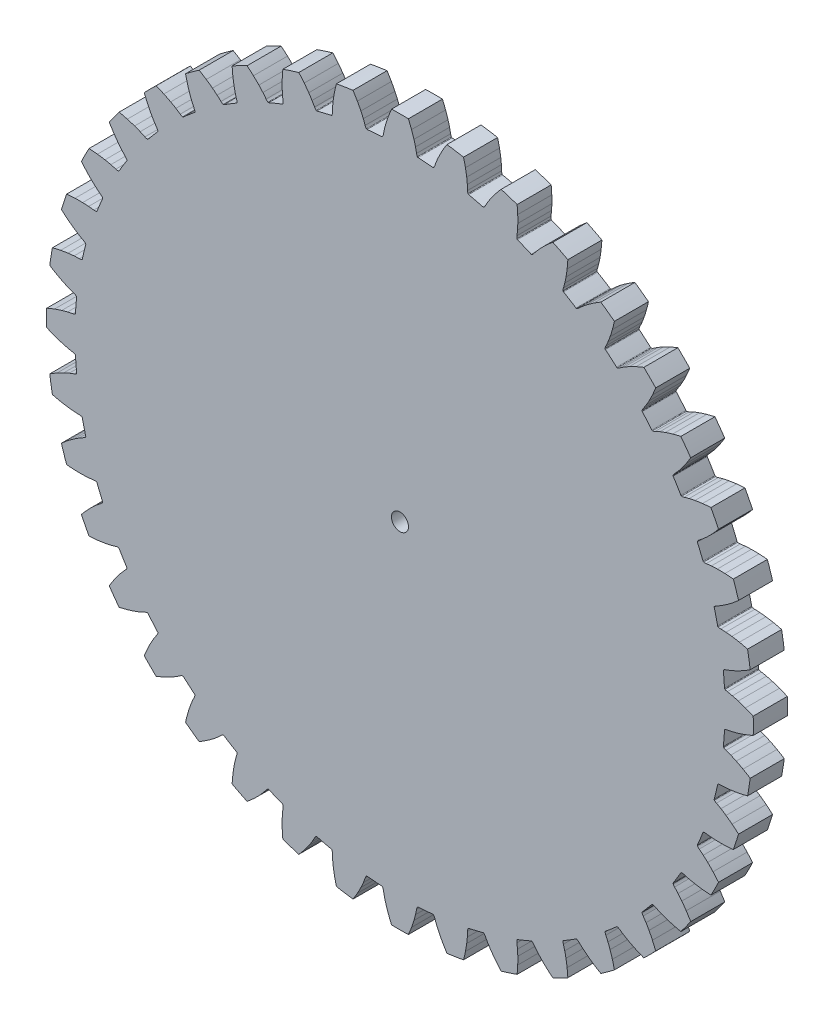
SolidWorks part; units mm, degrees
ref_plane "Front Plane" through (0, 0, 0) normal (0, 0, 1) x (1, 0, 0)
ref_plane "Top Plane" through (0, 0, 0) normal (0, 1, 0) x (1, 0, 0)
ref_plane "Right Plane" through (0, 0, 0) normal (1, 0, 0) x (0, 0, -1)
sketch "Model" plane through (0, 0, 0) normal (0, 0, 1) x (1, 0, 0)
  arc A1 (60.4326, -4.7561) -> (60.5251, -3.3796) centre (0, 0) ccw
  arc A2 (60.6099, -3.2458) -> (60.5251, -3.3796) centre (60.6875, -3.3887) ccw
  arc A3 (61.0557, -3.0916) -> (60.6099, -3.2458) centre (61.2975, -4.5122) ccw
  arc A4 (61.0557, -3.0916) -> (62.0044, -2.8977) centre (58.5908, 11.3846) ccw
  arc A5 (62.0044, -2.8977) -> (63.0847, -2.6067) centre (57.4472, 16.1693) ccw
  arc A6 (63.0847, -2.6067) -> (64.4306, -2.1546) centre (56.7644, 18.4435) ccw
  arc A7 (64.4306, -2.1546) -> (65.8858, -1.5642) centre (55.0531, 23.0418) ccw
  arc A8 (65.8858, -1.5642) -> (65.8858, 1.5642) centre (0, 0) ccw
  arc A9 (65.8858, 1.5642) -> (64.4306, 2.1546) centre (55.0531, -23.0418) ccw
  arc A10 (64.4306, 2.1546) -> (63.0847, 2.6067) centre (56.7644, -18.4435) ccw
  arc A11 (63.0847, 2.6067) -> (62.0044, 2.8977) centre (57.4472, -16.1693) ccw
  arc A12 (62.0044, 2.8977) -> (61.0557, 3.0916) centre (58.5908, -11.3846) ccw
  arc A13 (60.6099, 3.2458) -> (61.0557, 3.0916) centre (61.2975, 4.5122) ccw
  arc A14 (60.5251, 3.3796) -> (60.6099, 3.2458) centre (60.6875, 3.3887) ccw
  arc A15 (60.5251, 3.3796) -> (60.3087, 6.1302) centre (0, 0) ccw
  arc A16 (60.3715, 6.2757) -> (60.3087, 6.1302) centre (60.4705, 6.1466) ccw
  arc A17 (60.7876, 6.4977) -> (60.3715, 6.2757) centre (61.2487, 5.1324) ccw
  arc A18 (60.7876, 6.4977) -> (61.6943, 6.8376) centre (56.0885, 20.41) ccw
  arc A19 (61.6943, 6.8376) -> (62.7158, 7.294) centre (54.2105, 24.957) ccw
  arc A20 (62.7158, 7.294) -> (63.9745, 7.9511) centre (53.1804, 27.0964) ccw
  arc A21 (63.9745, 7.9511) -> (65.3193, 8.7619) centre (50.7708, 31.3703) ccw
  arc A22 (65.3193, 8.7619) -> (64.8299, 11.8517) centre (0, 0) ccw
  arc A23 (64.8299, 11.8517) -> (63.3003, 12.2073) centre (57.9798, -14.1459) ccw
  arc A24 (63.3003, 12.2073) -> (61.9002, 12.4432) centre (58.9508, -9.3365) ccw
  arc A25 (61.9002, 12.4432) -> (60.7877, 12.5616) centre (59.2694, -6.9835) ccw
  arc A26 (60.7877, 12.5616) -> (59.8203, 12.6047) centre (59.6504, -2.0788) ccw
  arc A27 (59.356, 12.6873) -> (59.8203, 12.6047) centre (59.837, 14.0457) ccw
  arc A28 (59.2513, 12.8063) -> (59.356, 12.6873) centre (59.4102, 12.8406) ccw
  arc A29 (59.2513, 12.8063) -> (58.6072, 15.4891) centre (0, 0) ccw
  arc A30 (58.6465, 15.6426) -> (58.6072, 15.4891) centre (58.7644, 15.5306) ccw
  arc A31 (59.0227, 15.9269) -> (58.6465, 15.6426) centre (59.6918, 14.6506) ccw
  arc A32 (59.0227, 15.9269) -> (59.8651, 16.4045) centre (52.2052, 28.9329) ccw
  arc A33 (59.8651, 16.4045) -> (60.8026, 17.0152) centre (49.639, 33.1301) ccw
  arc A34 (60.8026, 17.0152) -> (61.943, 17.861) centre (48.2868, 35.082) ccw
  arc A35 (61.943, 17.861) -> (63.1444, 18.8722) centre (45.2383, 38.9263) ccw
  arc A36 (63.1444, 18.8722) -> (62.1777, 21.8474) centre (0, 0) ccw
  arc A37 (62.1777, 21.8474) -> (60.6114, 21.9594) centre (59.4789, -4.9017) ccw
  arc A38 (60.6114, 21.9594) -> (59.1916, 21.9733) centre (59.6855, 0.0004) ccw
  arc A39 (59.1916, 21.9733) -> (58.0742, 21.9163) centre (59.6322, 2.3742) ccw
  arc A40 (58.0742, 21.9163) -> (57.112, 21.8075) centre (59.2412, 7.2782) ccw
  arc A41 (56.6405, 21.8164) -> (57.112, 21.8075) centre (56.9031, 23.2334) ccw
  arc A42 (56.5185, 21.9175) -> (56.6405, 21.8164) centre (56.6701, 21.9763) ccw
  arc A43 (56.5185, 21.9175) -> (55.4626, 24.4666) centre (0, 0) ccw
  arc A44 (55.4774, 24.6243) -> (55.4626, 24.4666) centre (55.6114, 24.5322) ccw
  arc A45 (55.8045, 24.9641) -> (55.4774, 24.6243) centre (56.665, 23.8081) ccw
  arc A46 (55.8045, 24.9641) -> (56.5618, 25.5675) centre (47.0363, 36.7434) ccw
  arc A47 (56.5618, 25.5675) -> (57.3922, 26.3173) centre (43.8451, 40.4875) ccw
  arc A48 (57.3922, 26.3173) -> (58.3863, 27.3311) centre (42.2043, 42.2038) ccw
  arc A49 (58.3863, 27.3311) -> (59.4147, 28.5178) centre (38.5919, 45.5239) ccw
  arc A50 (59.4147, 28.5178) -> (57.9945, 31.3052) centre (0, 0) ccw
  arc A51 (57.9945, 31.3052) -> (56.4299, 31.1707) centre (59.5134, 4.4632) ccw
  arc A52 (56.4299, 31.1707) -> (55.0254, 30.9624) centre (58.9507, 9.3372) ccw
  arc A53 (55.0254, 30.9624) -> (53.9308, 30.7312) centre (58.5266, 11.6735) ccw
  arc A54 (53.9308, 30.7312) -> (52.9974, 30.4733) centre (57.3733, 16.456) ccw
  arc A55 (52.5303, 30.4083) -> (52.9974, 30.4733) centre (52.568, 31.8489) ccw
  arc A56 (52.394, 30.4891) -> (52.5303, 30.4083) centre (52.5345, 30.5709) ccw
  arc A57 (52.394, 30.4891) -> (50.9524, 32.8416) centre (0, 0) ccw
  arc A58 (50.9423, 32.9997) -> (50.9524, 32.8416) centre (51.0891, 32.9297) ccw
  arc A59 (51.2123, 33.3865) -> (50.9423, 32.9997) centre (52.243, 32.3793) ccw
  arc A60 (51.2123, 33.3865) -> (51.8658, 34.101) centre (40.7093, 43.6491) ccw
  arc A61 (51.8658, 34.101) -> (52.5687, 34.9714) centre (36.9717, 46.8479) ccw
  arc A62 (52.5687, 34.9714) -> (53.392, 36.1282) centre (35.0826, 48.2864) ccw
  arc A63 (53.392, 36.1282) -> (54.2221, 37.4613) centre (30.9953, 51.0006) ccw
  arc A64 (54.2221, 37.4613) -> (52.3833, 39.9921) centre (0, 0) ccw
  arc A65 (52.3833, 39.9921) -> (50.859, 39.6145) centre (58.0825, 13.7182) ccw
  arc A66 (50.859, 39.6145) -> (49.5044, 39.1891) centre (56.7642, 18.4442) ccw
  arc A67 (49.5044, 39.1891) -> (48.4594, 38.7895) centre (55.9799, 20.6854) ccw
  arc A68 (48.4594, 38.7895) -> (47.5779, 38.3888) centre (54.0927, 25.2285) ccw
  arc A69 (47.1266, 38.2515) -> (47.5779, 38.3888) centre (46.9385, 39.6803) ccw
  arc A70 (46.9794, 38.31) -> (47.1266, 38.2515) centre (47.1054, 38.4128) ccw
  arc A71 (46.9794, 38.31) -> (45.1875, 40.408) centre (0, 0) ccw
  arc A72 (45.1528, 40.5626) -> (45.1875, 40.408) centre (45.3087, 40.5164) ccw
  arc A73 (45.359, 40.9868) -> (45.1528, 40.5626) centre (46.5345, 40.1533) ccw
  arc A74 (45.359, 40.9868) -> (45.8927, 41.7947) centre (33.3799, 49.4801) ccw
  arc A75 (45.8927, 41.7947) -> (46.4508, 42.7644) centre (29.1879, 52.0548) ccw
  arc A76 (46.4508, 42.7644) -> (47.0829, 44.0358) centre (27.097, 53.1801) ccw
  arc A77 (47.0829, 44.0358) -> (47.6943, 45.4822) centre (22.6354, 55.2214) ccw
  arc A78 (47.6943, 45.4822) -> (45.4822, 47.6943) centre (0, 0) ccw
  arc A79 (45.4822, 47.6943) -> (44.0358, 47.0829) centre (55.2214, 22.6354) ccw
  arc A80 (44.0358, 47.0829) -> (42.7644, 46.4508) centre (53.1801, 27.097) ccw
  arc A81 (42.7644, 46.4508) -> (41.7947, 45.8927) centre (52.0548, 29.1879) ccw
  arc A82 (41.7947, 45.8927) -> (40.9868, 45.359) centre (49.4801, 33.3799) ccw
  arc A83 (40.5626, 45.1528) -> (40.9868, 45.359) centre (40.1533, 46.5345) ccw
  arc A84 (40.408, 45.1875) -> (40.5626, 45.1528) centre (40.5164, 45.3087) ccw
  arc A85 (40.408, 45.1875) -> (38.31, 46.9794) centre (0, 0) ccw
  arc A86 (38.2515, 47.1266) -> (38.31, 46.9794) centre (38.4128, 47.1054) ccw
  arc A87 (38.3888, 47.5779) -> (38.2515, 47.1266) centre (39.6803, 46.9385) ccw
  arc A88 (38.3888, 47.5779) -> (38.7895, 48.4594) centre (25.2285, 54.0927) ccw
  arc A89 (38.7895, 48.4594) -> (39.1891, 49.5044) centre (20.6854, 55.9799) ccw
  arc A90 (39.1891, 49.5044) -> (39.6145, 50.859) centre (18.4442, 56.7642) ccw
  arc A91 (39.6145, 50.859) -> (39.9921, 52.3833) centre (13.7182, 58.0825) ccw
  arc A92 (39.9921, 52.3833) -> (37.4613, 54.2221) centre (0, 0) ccw
  arc A93 (37.4613, 54.2221) -> (36.1282, 53.392) centre (51.0006, 30.9953) ccw
  arc A94 (36.1282, 53.392) -> (34.9714, 52.5687) centre (48.2864, 35.0826) ccw
  arc A95 (34.9714, 52.5687) -> (34.101, 51.8658) centre (46.8479, 36.9717) ccw
  arc A96 (34.101, 51.8658) -> (33.3865, 51.2123) centre (43.6491, 40.7093) ccw
  arc A97 (32.9997, 50.9423) -> (33.3865, 51.2123) centre (32.3793, 52.243) ccw
  arc A98 (32.8416, 50.9524) -> (32.9997, 50.9423) centre (32.9297, 51.0891) ccw
  arc A99 (32.8416, 50.9524) -> (30.4891, 52.394) centre (0, 0) ccw
  arc A100 (30.4083, 52.5303) -> (30.4891, 52.394) centre (30.5709, 52.5345) ccw
  arc A101 (30.4733, 52.9974) -> (30.4083, 52.5303) centre (31.8489, 52.568) ccw
  arc A102 (30.4733, 52.9974) -> (30.7312, 53.9308) centre (16.456, 57.3733) ccw
  arc A103 (30.7312, 53.9308) -> (30.9624, 55.0254) centre (11.6735, 58.5266) ccw
  arc A104 (30.9624, 55.0254) -> (31.1707, 56.4299) centre (9.3372, 58.9507) ccw
  arc A105 (31.1707, 56.4299) -> (31.3052, 57.9945) centre (4.4632, 59.5134) ccw
  arc A106 (31.3052, 57.9945) -> (28.5178, 59.4147) centre (0, 0) ccw
  arc A107 (28.5178, 59.4147) -> (27.3311, 58.3863) centre (45.5239, 38.5919) ccw
  arc A108 (27.3311, 58.3863) -> (26.3173, 57.3922) centre (42.2038, 42.2043) ccw
  arc A109 (26.3173, 57.3922) -> (25.5675, 56.5618) centre (40.4875, 43.8451) ccw
  arc A110 (25.5675, 56.5618) -> (24.9641, 55.8045) centre (36.7434, 47.0363) ccw
  arc A111 (24.6243, 55.4774) -> (24.9641, 55.8045) centre (23.8081, 56.665) ccw
  arc A112 (24.4666, 55.4626) -> (24.6243, 55.4774) centre (24.5322, 55.6114) ccw
  arc A113 (24.4666, 55.4626) -> (21.9175, 56.5185) centre (0, 0) ccw
  arc A114 (21.8164, 56.6405) -> (21.9175, 56.5185) centre (21.9763, 56.6701) ccw
  arc A115 (21.8075, 57.112) -> (21.8164, 56.6405) centre (23.2334, 56.9031) ccw
  arc A116 (21.8075, 57.112) -> (21.9163, 58.0742) centre (7.2782, 59.2412) ccw
  arc A117 (21.9163, 58.0742) -> (21.9733, 59.1916) centre (2.3742, 59.6322) ccw
  arc A118 (21.9733, 59.1916) -> (21.9594, 60.6114) centre (0.0004, 59.6855) ccw
  arc A119 (21.9594, 60.6114) -> (21.8474, 62.1777) centre (-4.9017, 59.4789) ccw
  arc A120 (21.8474, 62.1777) -> (18.8722, 63.1444) centre (0, 0) ccw
  arc A121 (18.8722, 63.1444) -> (17.861, 61.943) centre (38.9263, 45.2383) ccw
  arc A122 (17.861, 61.943) -> (17.0152, 60.8026) centre (35.082, 48.2868) ccw
  arc A123 (17.0152, 60.8026) -> (16.4045, 59.8651) centre (33.1301, 49.639) ccw
  arc A124 (16.4045, 59.8651) -> (15.9269, 59.0227) centre (28.9329, 52.2052) ccw
  arc A125 (15.6426, 58.6465) -> (15.9269, 59.0227) centre (14.6506, 59.6918) ccw
  arc A126 (15.4891, 58.6072) -> (15.6426, 58.6465) centre (15.5306, 58.7644) ccw
  arc A127 (15.4891, 58.6072) -> (12.8063, 59.2513) centre (0, 0) ccw
  arc A128 (12.6873, 59.356) -> (12.8063, 59.2513) centre (12.8406, 59.4102) ccw
  arc A129 (12.6047, 59.8203) -> (12.6873, 59.356) centre (14.0457, 59.837) ccw
  arc A130 (12.6047, 59.8203) -> (12.5616, 60.7877) centre (-2.0788, 59.6504) ccw
  arc A131 (12.5616, 60.7877) -> (12.4432, 61.9002) centre (-6.9835, 59.2694) ccw
  arc A132 (12.4432, 61.9002) -> (12.2073, 63.3003) centre (-9.3365, 58.9508) ccw
  arc A133 (12.2073, 63.3003) -> (11.8517, 64.8299) centre (-14.1459, 57.9798) ccw
  arc A134 (11.8517, 64.8299) -> (8.7619, 65.3193) centre (0, 0) ccw
  arc A135 (8.7619, 65.3193) -> (7.9511, 63.9745) centre (31.3703, 50.7708) ccw
  arc A136 (7.9511, 63.9745) -> (7.294, 62.7158) centre (27.0964, 53.1804) ccw
  arc A137 (7.294, 62.7158) -> (6.8376, 61.6943) centre (24.957, 54.2105) ccw
  arc A138 (6.8376, 61.6943) -> (6.4977, 60.7876) centre (20.41, 56.0885) ccw
  arc A139 (6.2757, 60.3715) -> (6.4977, 60.7876) centre (5.1324, 61.2487) ccw
  arc A140 (6.1302, 60.3087) -> (6.2757, 60.3715) centre (6.1466, 60.4705) ccw
  arc A141 (6.1302, 60.3087) -> (3.3796, 60.5251) centre (0, 0) ccw
  arc A142 (3.2458, 60.6099) -> (3.3796, 60.5251) centre (3.3887, 60.6875) ccw
  arc A143 (3.0916, 61.0557) -> (3.2458, 60.6099) centre (4.5122, 61.2975) ccw
  arc A144 (3.0916, 61.0557) -> (2.8977, 62.0044) centre (-11.3846, 58.5908) ccw
  arc A145 (2.8977, 62.0044) -> (2.6067, 63.0847) centre (-16.1693, 57.4472) ccw
  arc A146 (2.6067, 63.0847) -> (2.1546, 64.4306) centre (-18.4435, 56.7644) ccw
  arc A147 (2.1546, 64.4306) -> (1.5642, 65.8858) centre (-23.0418, 55.0531) ccw
  arc A148 (1.5642, 65.8858) -> (-1.5642, 65.8858) centre (0, 0) ccw
  arc A149 (-1.5642, 65.8858) -> (-2.1546, 64.4306) centre (23.0418, 55.0531) ccw
  arc A150 (-2.1546, 64.4306) -> (-2.6067, 63.0847) centre (18.4435, 56.7644) ccw
  arc A151 (-2.6067, 63.0847) -> (-2.8977, 62.0044) centre (16.1693, 57.4472) ccw
  arc A152 (-2.8977, 62.0044) -> (-3.0916, 61.0557) centre (11.3846, 58.5908) ccw
  arc A153 (-3.2458, 60.6099) -> (-3.0916, 61.0557) centre (-4.5122, 61.2975) ccw
  arc A154 (-3.3796, 60.5251) -> (-3.2458, 60.6099) centre (-3.3887, 60.6875) ccw
  arc A155 (-3.3796, 60.5251) -> (-6.1302, 60.3087) centre (0, 0) ccw
  arc A156 (-6.2757, 60.3715) -> (-6.1302, 60.3087) centre (-6.1466, 60.4705) ccw
  arc A157 (-6.4977, 60.7876) -> (-6.2757, 60.3715) centre (-5.1324, 61.2487) ccw
  arc A158 (-6.4977, 60.7876) -> (-6.8376, 61.6943) centre (-20.41, 56.0885) ccw
  arc A159 (-6.8376, 61.6943) -> (-7.294, 62.7158) centre (-24.957, 54.2105) ccw
  arc A160 (-7.294, 62.7158) -> (-7.9511, 63.9745) centre (-27.0964, 53.1804) ccw
  arc A161 (-7.9511, 63.9745) -> (-8.7619, 65.3193) centre (-31.3703, 50.7708) ccw
  arc A162 (-8.7619, 65.3193) -> (-11.8517, 64.8299) centre (0, 0) ccw
  arc A163 (-11.8517, 64.8299) -> (-12.2073, 63.3003) centre (14.1459, 57.9798) ccw
  arc A164 (-12.2073, 63.3003) -> (-12.4432, 61.9002) centre (9.3365, 58.9508) ccw
  arc A165 (-12.4432, 61.9002) -> (-12.5616, 60.7877) centre (6.9835, 59.2694) ccw
  arc A166 (-12.5616, 60.7877) -> (-12.6047, 59.8203) centre (2.0788, 59.6504) ccw
  arc A167 (-12.6873, 59.356) -> (-12.6047, 59.8203) centre (-14.0457, 59.837) ccw
  arc A168 (-12.8063, 59.2513) -> (-12.6873, 59.356) centre (-12.8406, 59.4102) ccw
  arc A169 (-12.8063, 59.2513) -> (-15.4891, 58.6072) centre (0, 0) ccw
  arc A170 (-15.6426, 58.6465) -> (-15.4891, 58.6072) centre (-15.5306, 58.7644) ccw
  arc A171 (-15.9269, 59.0227) -> (-15.6426, 58.6465) centre (-14.6506, 59.6918) ccw
  arc A172 (-15.9269, 59.0227) -> (-16.4045, 59.8651) centre (-28.9329, 52.2052) ccw
  arc A173 (-16.4045, 59.8651) -> (-17.0152, 60.8026) centre (-33.1301, 49.639) ccw
  arc A174 (-17.0152, 60.8026) -> (-17.861, 61.943) centre (-35.082, 48.2868) ccw
  arc A175 (-17.861, 61.943) -> (-18.8722, 63.1444) centre (-38.9263, 45.2383) ccw
  arc A176 (-18.8722, 63.1444) -> (-21.8474, 62.1777) centre (0, 0) ccw
  arc A177 (-21.8474, 62.1777) -> (-21.9594, 60.6114) centre (4.9017, 59.4789) ccw
  arc A178 (-21.9594, 60.6114) -> (-21.9733, 59.1916) centre (-0.0004, 59.6855) ccw
  arc A179 (-21.9733, 59.1916) -> (-21.9163, 58.0742) centre (-2.3742, 59.6322) ccw
  arc A180 (-21.9163, 58.0742) -> (-21.8075, 57.112) centre (-7.2782, 59.2412) ccw
  arc A181 (-21.8164, 56.6405) -> (-21.8075, 57.112) centre (-23.2334, 56.9031) ccw
  arc A182 (-21.9175, 56.5185) -> (-21.8164, 56.6405) centre (-21.9763, 56.6701) ccw
  arc A183 (-21.9175, 56.5185) -> (-24.4666, 55.4626) centre (0, 0) ccw
  arc A184 (-24.6243, 55.4774) -> (-24.4666, 55.4626) centre (-24.5322, 55.6114) ccw
  arc A185 (-24.9641, 55.8045) -> (-24.6243, 55.4774) centre (-23.8081, 56.665) ccw
  arc A186 (-24.9641, 55.8045) -> (-25.5675, 56.5618) centre (-36.7434, 47.0363) ccw
  arc A187 (-25.5675, 56.5618) -> (-26.3173, 57.3922) centre (-40.4875, 43.8451) ccw
  arc A188 (-26.3173, 57.3922) -> (-27.3311, 58.3863) centre (-42.2038, 42.2043) ccw
  arc A189 (-27.3311, 58.3863) -> (-28.5178, 59.4147) centre (-45.5239, 38.5919) ccw
  arc A190 (-28.5178, 59.4147) -> (-31.3052, 57.9945) centre (0, 0) ccw
  arc A191 (-31.3052, 57.9945) -> (-31.1707, 56.4299) centre (-4.4632, 59.5134) ccw
  arc A192 (-31.1707, 56.4299) -> (-30.9624, 55.0254) centre (-9.3372, 58.9507) ccw
  arc A193 (-30.9624, 55.0254) -> (-30.7312, 53.9308) centre (-11.6735, 58.5266) ccw
  arc A194 (-30.7312, 53.9308) -> (-30.4733, 52.9974) centre (-16.456, 57.3733) ccw
  arc A195 (-30.4083, 52.5303) -> (-30.4733, 52.9974) centre (-31.8489, 52.568) ccw
  arc A196 (-30.4891, 52.394) -> (-30.4083, 52.5303) centre (-30.5709, 52.5345) ccw
  arc A197 (-30.4891, 52.394) -> (-32.8416, 50.9524) centre (0, 0) ccw
  arc A198 (-32.9997, 50.9423) -> (-32.8416, 50.9524) centre (-32.9297, 51.0891) ccw
  arc A199 (-33.3865, 51.2123) -> (-32.9997, 50.9423) centre (-32.3793, 52.243) ccw
  arc A200 (-33.3865, 51.2123) -> (-34.101, 51.8658) centre (-43.6491, 40.7093) ccw
  arc A201 (-34.101, 51.8658) -> (-34.9714, 52.5687) centre (-46.8479, 36.9717) ccw
  arc A202 (-34.9714, 52.5687) -> (-36.1282, 53.392) centre (-48.2864, 35.0826) ccw
  arc A203 (-36.1282, 53.392) -> (-37.4613, 54.2221) centre (-51.0006, 30.9953) ccw
  arc A204 (-37.4613, 54.2221) -> (-39.9921, 52.3833) centre (0, 0) ccw
  arc A205 (-39.9921, 52.3833) -> (-39.6145, 50.859) centre (-13.7182, 58.0825) ccw
  arc A206 (-39.6145, 50.859) -> (-39.1891, 49.5044) centre (-18.4442, 56.7642) ccw
  arc A207 (-39.1891, 49.5044) -> (-38.7895, 48.4594) centre (-20.6854, 55.9799) ccw
  arc A208 (-38.7895, 48.4594) -> (-38.3888, 47.5779) centre (-25.2285, 54.0927) ccw
  arc A209 (-38.2515, 47.1266) -> (-38.3888, 47.5779) centre (-39.6803, 46.9385) ccw
  arc A210 (-38.31, 46.9794) -> (-38.2515, 47.1266) centre (-38.4128, 47.1054) ccw
  arc A211 (-38.31, 46.9794) -> (-40.408, 45.1875) centre (0, 0) ccw
  arc A212 (-40.5626, 45.1528) -> (-40.408, 45.1875) centre (-40.5164, 45.3087) ccw
  arc A213 (-40.9868, 45.359) -> (-40.5626, 45.1528) centre (-40.1533, 46.5345) ccw
  arc A214 (-40.9868, 45.359) -> (-41.7947, 45.8927) centre (-49.4801, 33.3799) ccw
  arc A215 (-41.7947, 45.8927) -> (-42.7644, 46.4508) centre (-52.0548, 29.1879) ccw
  arc A216 (-42.7644, 46.4508) -> (-44.0358, 47.0829) centre (-53.1801, 27.097) ccw
  arc A217 (-44.0358, 47.0829) -> (-45.4822, 47.6943) centre (-55.2214, 22.6354) ccw
  arc A218 (-45.4822, 47.6943) -> (-47.6943, 45.4822) centre (0, 0) ccw
  arc A219 (-47.6943, 45.4822) -> (-47.0829, 44.0358) centre (-22.6354, 55.2214) ccw
  arc A220 (-47.0829, 44.0358) -> (-46.4508, 42.7644) centre (-27.097, 53.1801) ccw
  arc A221 (-46.4508, 42.7644) -> (-45.8927, 41.7947) centre (-29.1879, 52.0548) ccw
  arc A222 (-45.8927, 41.7947) -> (-45.359, 40.9868) centre (-33.3799, 49.4801) ccw
  arc A223 (-45.1528, 40.5626) -> (-45.359, 40.9868) centre (-46.5345, 40.1533) ccw
  arc A224 (-45.1875, 40.408) -> (-45.1528, 40.5626) centre (-45.3087, 40.5164) ccw
  arc A225 (-45.1875, 40.408) -> (-46.9794, 38.31) centre (0, 0) ccw
  arc A226 (-47.1266, 38.2515) -> (-46.9794, 38.31) centre (-47.1054, 38.4128) ccw
  arc A227 (-47.5779, 38.3888) -> (-47.1266, 38.2515) centre (-46.9385, 39.6803) ccw
  arc A228 (-47.5779, 38.3888) -> (-48.4594, 38.7895) centre (-54.0927, 25.2285) ccw
  arc A229 (-48.4594, 38.7895) -> (-49.5044, 39.1891) centre (-55.9799, 20.6854) ccw
  arc A230 (-49.5044, 39.1891) -> (-50.859, 39.6145) centre (-56.7642, 18.4442) ccw
  arc A231 (-50.859, 39.6145) -> (-52.3833, 39.9921) centre (-58.0825, 13.7182) ccw
  arc A232 (-52.3833, 39.9921) -> (-54.2221, 37.4613) centre (0, 0) ccw
  arc A233 (-54.2221, 37.4613) -> (-53.392, 36.1282) centre (-30.9953, 51.0006) ccw
  arc A234 (-53.392, 36.1282) -> (-52.5687, 34.9714) centre (-35.0826, 48.2864) ccw
  arc A235 (-52.5687, 34.9714) -> (-51.8658, 34.101) centre (-36.9717, 46.8479) ccw
  arc A236 (-51.8658, 34.101) -> (-51.2123, 33.3865) centre (-40.7093, 43.6491) ccw
  arc A237 (-50.9423, 32.9997) -> (-51.2123, 33.3865) centre (-52.243, 32.3793) ccw
  arc A238 (-50.9524, 32.8416) -> (-50.9423, 32.9997) centre (-51.0891, 32.9297) ccw
  arc A239 (-50.9524, 32.8416) -> (-52.394, 30.4891) centre (0, 0) ccw
  arc A240 (-52.5303, 30.4083) -> (-52.394, 30.4891) centre (-52.5345, 30.5709) ccw
  arc A241 (-52.9974, 30.4733) -> (-52.5303, 30.4083) centre (-52.568, 31.8489) ccw
  arc A242 (-52.9974, 30.4733) -> (-53.9308, 30.7312) centre (-57.3733, 16.456) ccw
  arc A243 (-53.9308, 30.7312) -> (-55.0254, 30.9624) centre (-58.5266, 11.6735) ccw
  arc A244 (-55.0254, 30.9624) -> (-56.4299, 31.1707) centre (-58.9507, 9.3372) ccw
  arc A245 (-56.4299, 31.1707) -> (-57.9945, 31.3052) centre (-59.5134, 4.4632) ccw
  arc A246 (-57.9945, 31.3052) -> (-59.4147, 28.5178) centre (0, 0) ccw
  arc A247 (-59.4147, 28.5178) -> (-58.3863, 27.3311) centre (-38.5919, 45.5239) ccw
  arc A248 (-58.3863, 27.3311) -> (-57.3922, 26.3173) centre (-42.2043, 42.2038) ccw
  arc A249 (-57.3922, 26.3173) -> (-56.5618, 25.5675) centre (-43.8451, 40.4875) ccw
  arc A250 (-56.5618, 25.5675) -> (-55.8045, 24.9641) centre (-47.0363, 36.7434) ccw
  arc A251 (-55.4774, 24.6243) -> (-55.8045, 24.9641) centre (-56.665, 23.8081) ccw
  arc A252 (-55.4626, 24.4666) -> (-55.4774, 24.6243) centre (-55.6114, 24.5322) ccw
  arc A253 (-55.4626, 24.4666) -> (-56.5185, 21.9175) centre (0, 0) ccw
  arc A254 (-56.6405, 21.8164) -> (-56.5185, 21.9175) centre (-56.6701, 21.9763) ccw
  arc A255 (-57.112, 21.8075) -> (-56.6405, 21.8164) centre (-56.9031, 23.2334) ccw
  arc A256 (-57.112, 21.8075) -> (-58.0742, 21.9163) centre (-59.2412, 7.2782) ccw
  arc A257 (-58.0742, 21.9163) -> (-59.1916, 21.9733) centre (-59.6322, 2.3742) ccw
  arc A258 (-59.1916, 21.9733) -> (-60.6114, 21.9594) centre (-59.6855, 0.0004) ccw
  arc A259 (-60.6114, 21.9594) -> (-62.1777, 21.8474) centre (-59.4789, -4.9017) ccw
  arc A260 (-62.1777, 21.8474) -> (-63.1444, 18.8722) centre (0, 0) ccw
  arc A261 (-63.1444, 18.8722) -> (-61.943, 17.861) centre (-45.2383, 38.9263) ccw
  arc A262 (-61.943, 17.861) -> (-60.8026, 17.0152) centre (-48.2868, 35.082) ccw
  arc A263 (-60.8026, 17.0152) -> (-59.8651, 16.4045) centre (-49.639, 33.1301) ccw
  arc A264 (-59.8651, 16.4045) -> (-59.0227, 15.9269) centre (-52.2052, 28.9329) ccw
  arc A265 (-58.6465, 15.6426) -> (-59.0227, 15.9269) centre (-59.6918, 14.6506) ccw
  arc A266 (-58.6072, 15.4891) -> (-58.6465, 15.6426) centre (-58.7644, 15.5306) ccw
  arc A267 (-58.6072, 15.4891) -> (-59.2513, 12.8063) centre (0, 0) ccw
  arc A268 (-59.356, 12.6873) -> (-59.2513, 12.8063) centre (-59.4102, 12.8406) ccw
  arc A269 (-59.8203, 12.6047) -> (-59.356, 12.6873) centre (-59.837, 14.0457) ccw
  arc A270 (-59.8203, 12.6047) -> (-60.7877, 12.5616) centre (-59.6504, -2.0788) ccw
  arc A271 (-60.7877, 12.5616) -> (-61.9002, 12.4432) centre (-59.2694, -6.9835) ccw
  arc A272 (-61.9002, 12.4432) -> (-63.3003, 12.2073) centre (-58.9508, -9.3365) ccw
  arc A273 (-63.3003, 12.2073) -> (-64.8299, 11.8517) centre (-57.9798, -14.1459) ccw
  arc A274 (-64.8299, 11.8517) -> (-65.3193, 8.7619) centre (0, 0) ccw
  arc A275 (-65.3193, 8.7619) -> (-63.9745, 7.9511) centre (-50.7708, 31.3703) ccw
  arc A276 (-63.9745, 7.9511) -> (-62.7158, 7.294) centre (-53.1804, 27.0964) ccw
  arc A277 (-62.7158, 7.294) -> (-61.6943, 6.8376) centre (-54.2105, 24.957) ccw
  arc A278 (-61.6943, 6.8376) -> (-60.7876, 6.4977) centre (-56.0885, 20.41) ccw
  arc A279 (-60.3715, 6.2757) -> (-60.7876, 6.4977) centre (-61.2487, 5.1324) ccw
  arc A280 (-60.3087, 6.1302) -> (-60.3715, 6.2757) centre (-60.4705, 6.1466) ccw
  arc A281 (-60.3087, 6.1302) -> (-60.5251, 3.3796) centre (0, 0) ccw
  arc A282 (-60.6099, 3.2458) -> (-60.5251, 3.3796) centre (-60.6875, 3.3887) ccw
  arc A283 (-61.0557, 3.0916) -> (-60.6099, 3.2458) centre (-61.2975, 4.5122) ccw
  arc A284 (-61.0557, 3.0916) -> (-62.0044, 2.8977) centre (-58.5908, -11.3846) ccw
  arc A285 (-62.0044, 2.8977) -> (-63.0847, 2.6067) centre (-57.4472, -16.1693) ccw
  arc A286 (-63.0847, 2.6067) -> (-64.4306, 2.1546) centre (-56.7644, -18.4435) ccw
  arc A287 (-64.4306, 2.1546) -> (-65.8858, 1.5642) centre (-55.0531, -23.0418) ccw
  arc A288 (-65.8858, 1.5642) -> (-65.8858, -1.5642) centre (0, 0) ccw
  arc A289 (-65.8858, -1.5642) -> (-64.4306, -2.1546) centre (-55.0531, 23.0418) ccw
  arc A290 (-64.4306, -2.1546) -> (-63.0847, -2.6067) centre (-56.7644, 18.4435) ccw
  arc A291 (-63.0847, -2.6067) -> (-62.0044, -2.8977) centre (-57.4472, 16.1693) ccw
  arc A292 (-62.0044, -2.8977) -> (-61.0557, -3.0916) centre (-58.5908, 11.3846) ccw
  arc A293 (-60.6099, -3.2458) -> (-61.0557, -3.0916) centre (-61.2975, -4.5122) ccw
  arc A294 (-60.5251, -3.3796) -> (-60.6099, -3.2458) centre (-60.6875, -3.3887) ccw
  arc A295 (-60.5251, -3.3796) -> (-60.3087, -6.1302) centre (0, 0) ccw
  arc A296 (-60.3715, -6.2757) -> (-60.3087, -6.1302) centre (-60.4705, -6.1466) ccw
  arc A297 (-60.7876, -6.4977) -> (-60.3715, -6.2757) centre (-61.2487, -5.1324) ccw
  arc A298 (-60.7876, -6.4977) -> (-61.6943, -6.8376) centre (-56.0885, -20.41) ccw
  arc A299 (-61.6943, -6.8376) -> (-62.7158, -7.294) centre (-54.2105, -24.957) ccw
  arc A300 (-62.7158, -7.294) -> (-63.9745, -7.9511) centre (-53.1804, -27.0964) ccw
  arc A301 (-63.9745, -7.9511) -> (-65.3193, -8.7619) centre (-50.7708, -31.3703) ccw
  arc A302 (-65.3193, -8.7619) -> (-64.8299, -11.8517) centre (0, 0) ccw
  arc A303 (-64.8299, -11.8517) -> (-63.3003, -12.2073) centre (-57.9798, 14.1459) ccw
  arc A304 (-63.3003, -12.2073) -> (-61.9002, -12.4432) centre (-58.9508, 9.3365) ccw
  arc A305 (-61.9002, -12.4432) -> (-60.7877, -12.5616) centre (-59.2694, 6.9835) ccw
  arc A306 (-60.7877, -12.5616) -> (-59.8203, -12.6047) centre (-59.6504, 2.0788) ccw
  arc A307 (-59.356, -12.6873) -> (-59.8203, -12.6047) centre (-59.837, -14.0457) ccw
  arc A308 (-59.2513, -12.8063) -> (-59.356, -12.6873) centre (-59.4102, -12.8406) ccw
  arc A309 (-59.2513, -12.8063) -> (-58.6072, -15.4891) centre (0, 0) ccw
  arc A310 (-58.6465, -15.6426) -> (-58.6072, -15.4891) centre (-58.7644, -15.5306) ccw
  arc A311 (-59.0227, -15.9269) -> (-58.6465, -15.6426) centre (-59.6918, -14.6506) ccw
  arc A312 (-59.0227, -15.9269) -> (-59.8651, -16.4045) centre (-52.2052, -28.9329) ccw
  arc A313 (-59.8651, -16.4045) -> (-60.8026, -17.0152) centre (-49.639, -33.1301) ccw
  arc A314 (-60.8026, -17.0152) -> (-61.943, -17.861) centre (-48.2868, -35.082) ccw
  arc A315 (-61.943, -17.861) -> (-63.1444, -18.8722) centre (-45.2383, -38.9263) ccw
  arc A316 (-63.1444, -18.8722) -> (-62.1777, -21.8474) centre (0, 0) ccw
  arc A317 (-62.1777, -21.8474) -> (-60.6114, -21.9594) centre (-59.4789, 4.9017) ccw
  arc A318 (-60.6114, -21.9594) -> (-59.1916, -21.9733) centre (-59.6855, -0.0004) ccw
  arc A319 (-59.1916, -21.9733) -> (-58.0742, -21.9163) centre (-59.6322, -2.3742) ccw
  arc A320 (-58.0742, -21.9163) -> (-57.112, -21.8075) centre (-59.2412, -7.2782) ccw
  arc A321 (-56.6405, -21.8164) -> (-57.112, -21.8075) centre (-56.9031, -23.2334) ccw
  arc A322 (-56.5185, -21.9175) -> (-56.6405, -21.8164) centre (-56.6701, -21.9763) ccw
  arc A323 (-56.5185, -21.9175) -> (-55.4626, -24.4666) centre (0, 0) ccw
  arc A324 (-55.4774, -24.6243) -> (-55.4626, -24.4666) centre (-55.6114, -24.5322) ccw
  arc A325 (-55.8045, -24.9641) -> (-55.4774, -24.6243) centre (-56.665, -23.8081) ccw
  arc A326 (-55.8045, -24.9641) -> (-56.5618, -25.5675) centre (-47.0363, -36.7434) ccw
  arc A327 (-56.5618, -25.5675) -> (-57.3922, -26.3173) centre (-43.8451, -40.4875) ccw
  arc A328 (-57.3922, -26.3173) -> (-58.3863, -27.3311) centre (-42.2043, -42.2038) ccw
  arc A329 (-58.3863, -27.3311) -> (-59.4147, -28.5178) centre (-38.5919, -45.5239) ccw
  arc A330 (-59.4147, -28.5178) -> (-57.9945, -31.3052) centre (0, 0) ccw
  arc A331 (-57.9945, -31.3052) -> (-56.4299, -31.1707) centre (-59.5134, -4.4632) ccw
  arc A332 (-56.4299, -31.1707) -> (-55.0254, -30.9624) centre (-58.9507, -9.3372) ccw
  arc A333 (-55.0254, -30.9624) -> (-53.9308, -30.7312) centre (-58.5266, -11.6735) ccw
  arc A334 (-53.9308, -30.7312) -> (-52.9974, -30.4733) centre (-57.3733, -16.456) ccw
  arc A335 (-52.5303, -30.4083) -> (-52.9974, -30.4733) centre (-52.568, -31.8489) ccw
  arc A336 (-52.394, -30.4891) -> (-52.5303, -30.4083) centre (-52.5345, -30.5709) ccw
  arc A337 (-52.394, -30.4891) -> (-50.9524, -32.8416) centre (0, 0) ccw
  arc A338 (-50.9423, -32.9997) -> (-50.9524, -32.8416) centre (-51.0891, -32.9297) ccw
  arc A339 (-51.2123, -33.3865) -> (-50.9423, -32.9997) centre (-52.243, -32.3793) ccw
  arc A340 (-51.2123, -33.3865) -> (-51.8658, -34.101) centre (-40.7093, -43.6491) ccw
  arc A341 (-51.8658, -34.101) -> (-52.5687, -34.9714) centre (-36.9717, -46.8479) ccw
  arc A342 (-52.5687, -34.9714) -> (-53.392, -36.1282) centre (-35.0826, -48.2864) ccw
  arc A343 (-53.392, -36.1282) -> (-54.2221, -37.4613) centre (-30.9953, -51.0006) ccw
  arc A344 (-54.2221, -37.4613) -> (-52.3833, -39.9921) centre (0, 0) ccw
  arc A345 (-52.3833, -39.9921) -> (-50.859, -39.6145) centre (-58.0825, -13.7182) ccw
  arc A346 (-50.859, -39.6145) -> (-49.5044, -39.1891) centre (-56.7642, -18.4442) ccw
  arc A347 (-49.5044, -39.1891) -> (-48.4594, -38.7895) centre (-55.9799, -20.6854) ccw
  arc A348 (-48.4594, -38.7895) -> (-47.5779, -38.3888) centre (-54.0927, -25.2285) ccw
  arc A349 (-47.1266, -38.2515) -> (-47.5779, -38.3888) centre (-46.9385, -39.6803) ccw
  arc A350 (-46.9794, -38.31) -> (-47.1266, -38.2515) centre (-47.1054, -38.4128) ccw
  arc A351 (-46.9794, -38.31) -> (-45.1875, -40.408) centre (0, 0) ccw
  arc A352 (-45.1528, -40.5626) -> (-45.1875, -40.408) centre (-45.3087, -40.5164) ccw
  arc A353 (-45.359, -40.9868) -> (-45.1528, -40.5626) centre (-46.5345, -40.1533) ccw
  arc A354 (-45.359, -40.9868) -> (-45.8927, -41.7947) centre (-33.3799, -49.4801) ccw
  arc A355 (-45.8927, -41.7947) -> (-46.4508, -42.7644) centre (-29.1879, -52.0548) ccw
  arc A356 (-46.4508, -42.7644) -> (-47.0829, -44.0358) centre (-27.097, -53.1801) ccw
  arc A357 (-47.0829, -44.0358) -> (-47.6943, -45.4822) centre (-22.6354, -55.2214) ccw
  arc A358 (-47.6943, -45.4822) -> (-45.4822, -47.6943) centre (0, 0) ccw
  arc A359 (-45.4822, -47.6943) -> (-44.0358, -47.0829) centre (-55.2214, -22.6354) ccw
  arc A360 (-44.0358, -47.0829) -> (-42.7644, -46.4508) centre (-53.1801, -27.097) ccw
  arc A361 (-42.7644, -46.4508) -> (-41.7947, -45.8927) centre (-52.0548, -29.1879) ccw
  arc A362 (-41.7947, -45.8927) -> (-40.9868, -45.359) centre (-49.4801, -33.3799) ccw
  arc A363 (-40.5626, -45.1528) -> (-40.9868, -45.359) centre (-40.1533, -46.5345) ccw
  arc A364 (-40.408, -45.1875) -> (-40.5626, -45.1528) centre (-40.5164, -45.3087) ccw
  arc A365 (-40.408, -45.1875) -> (-38.31, -46.9794) centre (0, 0) ccw
  arc A366 (-38.2515, -47.1266) -> (-38.31, -46.9794) centre (-38.4128, -47.1054) ccw
  arc A367 (-38.3888, -47.5779) -> (-38.2515, -47.1266) centre (-39.6803, -46.9385) ccw
  arc A368 (-38.3888, -47.5779) -> (-38.7895, -48.4594) centre (-25.2285, -54.0927) ccw
  arc A369 (-38.7895, -48.4594) -> (-39.1891, -49.5044) centre (-20.6854, -55.9799) ccw
  arc A370 (-39.1891, -49.5044) -> (-39.6145, -50.859) centre (-18.4442, -56.7642) ccw
  arc A371 (-39.6145, -50.859) -> (-39.9921, -52.3833) centre (-13.7182, -58.0825) ccw
  arc A372 (-39.9921, -52.3833) -> (-37.4613, -54.2221) centre (0, 0) ccw
  arc A373 (-37.4613, -54.2221) -> (-36.1282, -53.392) centre (-51.0006, -30.9953) ccw
  arc A374 (-36.1282, -53.392) -> (-34.9714, -52.5687) centre (-48.2864, -35.0826) ccw
  arc A375 (-34.9714, -52.5687) -> (-34.101, -51.8658) centre (-46.8479, -36.9717) ccw
  arc A376 (-34.101, -51.8658) -> (-33.3865, -51.2123) centre (-43.6491, -40.7093) ccw
  arc A377 (-32.9997, -50.9423) -> (-33.3865, -51.2123) centre (-32.3793, -52.243) ccw
  arc A378 (-32.8416, -50.9524) -> (-32.9997, -50.9423) centre (-32.9297, -51.0891) ccw
  arc A379 (-32.8416, -50.9524) -> (-30.4891, -52.394) centre (0, 0) ccw
  arc A380 (-30.4083, -52.5303) -> (-30.4891, -52.394) centre (-30.5709, -52.5345) ccw
  arc A381 (-30.4733, -52.9974) -> (-30.4083, -52.5303) centre (-31.8489, -52.568) ccw
  arc A382 (-30.4733, -52.9974) -> (-30.7312, -53.9308) centre (-16.456, -57.3733) ccw
  arc A383 (-30.7312, -53.9308) -> (-30.9624, -55.0254) centre (-11.6735, -58.5266) ccw
  arc A384 (-30.9624, -55.0254) -> (-31.1707, -56.4299) centre (-9.3372, -58.9507) ccw
  arc A385 (-31.1707, -56.4299) -> (-31.3052, -57.9945) centre (-4.4632, -59.5134) ccw
  arc A386 (-31.3052, -57.9945) -> (-28.5178, -59.4147) centre (0, 0) ccw
  arc A387 (-28.5178, -59.4147) -> (-27.3311, -58.3863) centre (-45.5239, -38.5919) ccw
  arc A388 (-27.3311, -58.3863) -> (-26.3173, -57.3922) centre (-42.2038, -42.2043) ccw
  arc A389 (-26.3173, -57.3922) -> (-25.5675, -56.5618) centre (-40.4875, -43.8451) ccw
  arc A390 (-25.5675, -56.5618) -> (-24.9641, -55.8045) centre (-36.7434, -47.0363) ccw
  arc A391 (-24.6243, -55.4774) -> (-24.9641, -55.8045) centre (-23.8081, -56.665) ccw
  arc A392 (-24.4666, -55.4626) -> (-24.6243, -55.4774) centre (-24.5322, -55.6114) ccw
  arc A393 (-24.4666, -55.4626) -> (-21.9175, -56.5185) centre (0, 0) ccw
  arc A394 (-21.8164, -56.6405) -> (-21.9175, -56.5185) centre (-21.9763, -56.6701) ccw
  arc A395 (-21.8075, -57.112) -> (-21.8164, -56.6405) centre (-23.2334, -56.9031) ccw
  arc A396 (-21.8075, -57.112) -> (-21.9163, -58.0742) centre (-7.2782, -59.2412) ccw
  arc A397 (-21.9163, -58.0742) -> (-21.9733, -59.1916) centre (-2.3742, -59.6322) ccw
  arc A398 (-21.9733, -59.1916) -> (-21.9594, -60.6114) centre (-0.0004, -59.6855) ccw
  arc A399 (-21.9594, -60.6114) -> (-21.8474, -62.1777) centre (4.9017, -59.4789) ccw
  arc A400 (-21.8474, -62.1777) -> (-18.8722, -63.1444) centre (0, 0) ccw
  arc A401 (-18.8722, -63.1444) -> (-17.861, -61.943) centre (-38.9263, -45.2383) ccw
  arc A402 (-17.861, -61.943) -> (-17.0152, -60.8026) centre (-35.082, -48.2868) ccw
  arc A403 (-17.0152, -60.8026) -> (-16.4045, -59.8651) centre (-33.1301, -49.639) ccw
  arc A404 (-16.4045, -59.8651) -> (-15.9269, -59.0227) centre (-28.9329, -52.2052) ccw
  arc A405 (-15.6426, -58.6465) -> (-15.9269, -59.0227) centre (-14.6506, -59.6918) ccw
  arc A406 (-15.4891, -58.6072) -> (-15.6426, -58.6465) centre (-15.5306, -58.7644) ccw
  arc A407 (-15.4891, -58.6072) -> (-12.8063, -59.2513) centre (0, 0) ccw
  arc A408 (-12.6873, -59.356) -> (-12.8063, -59.2513) centre (-12.8406, -59.4102) ccw
  arc A409 (-12.6047, -59.8203) -> (-12.6873, -59.356) centre (-14.0457, -59.837) ccw
  arc A410 (-12.6047, -59.8203) -> (-12.5616, -60.7877) centre (2.0788, -59.6504) ccw
  arc A411 (-12.5616, -60.7877) -> (-12.4432, -61.9002) centre (6.9835, -59.2694) ccw
  arc A412 (-12.4432, -61.9002) -> (-12.2073, -63.3003) centre (9.3365, -58.9508) ccw
  arc A413 (-12.2073, -63.3003) -> (-11.8517, -64.8299) centre (14.1459, -57.9798) ccw
  arc A414 (-11.8517, -64.8299) -> (-8.7619, -65.3193) centre (0, 0) ccw
  arc A415 (-8.7619, -65.3193) -> (-7.9511, -63.9745) centre (-31.3703, -50.7708) ccw
  arc A416 (-7.9511, -63.9745) -> (-7.294, -62.7158) centre (-27.0964, -53.1804) ccw
  arc A417 (-7.294, -62.7158) -> (-6.8376, -61.6943) centre (-24.957, -54.2105) ccw
  arc A418 (-6.8376, -61.6943) -> (-6.4977, -60.7876) centre (-20.41, -56.0885) ccw
  arc A419 (-6.2757, -60.3715) -> (-6.4977, -60.7876) centre (-5.1324, -61.2487) ccw
  arc A420 (-6.1302, -60.3087) -> (-6.2757, -60.3715) centre (-6.1466, -60.4705) ccw
  arc A421 (-6.1302, -60.3087) -> (-3.3796, -60.5251) centre (0, 0) ccw
  arc A422 (-3.2458, -60.6099) -> (-3.3796, -60.5251) centre (-3.3887, -60.6875) ccw
  arc A423 (-3.0916, -61.0557) -> (-3.2458, -60.6099) centre (-4.5122, -61.2975) ccw
  arc A424 (-3.0916, -61.0557) -> (-2.8977, -62.0044) centre (11.3846, -58.5908) ccw
  arc A425 (-2.8977, -62.0044) -> (-2.6067, -63.0847) centre (16.1693, -57.4472) ccw
  arc A426 (-2.6067, -63.0847) -> (-2.1546, -64.4306) centre (18.4435, -56.7644) ccw
  arc A427 (-2.1546, -64.4306) -> (-1.5642, -65.8858) centre (23.0418, -55.0531) ccw
  arc A428 (-1.5642, -65.8858) -> (1.5642, -65.8858) centre (0, 0) ccw
  arc A429 (1.5642, -65.8858) -> (2.1546, -64.4306) centre (-23.0418, -55.0531) ccw
  arc A430 (2.1546, -64.4306) -> (2.6067, -63.0847) centre (-18.4435, -56.7644) ccw
  arc A431 (2.6067, -63.0847) -> (2.8977, -62.0044) centre (-16.1693, -57.4472) ccw
  arc A432 (2.8977, -62.0044) -> (3.0916, -61.0557) centre (-11.3846, -58.5908) ccw
  arc A433 (3.2458, -60.6099) -> (3.0916, -61.0557) centre (4.5122, -61.2975) ccw
  arc A434 (3.3796, -60.5251) -> (3.2458, -60.6099) centre (3.3887, -60.6875) ccw
  arc A435 (3.3796, -60.5251) -> (6.1302, -60.3087) centre (0, 0) ccw
  arc A436 (6.2757, -60.3715) -> (6.1302, -60.3087) centre (6.1466, -60.4705) ccw
  arc A437 (6.4977, -60.7876) -> (6.2757, -60.3715) centre (5.1324, -61.2487) ccw
  arc A438 (6.4977, -60.7876) -> (6.8376, -61.6943) centre (20.41, -56.0885) ccw
  arc A439 (6.8376, -61.6943) -> (7.294, -62.7158) centre (24.957, -54.2105) ccw
  arc A440 (7.294, -62.7158) -> (7.9511, -63.9745) centre (27.0964, -53.1804) ccw
  arc A441 (7.9511, -63.9745) -> (8.7619, -65.3193) centre (31.3703, -50.7708) ccw
  arc A442 (8.7619, -65.3193) -> (11.8517, -64.8299) centre (0, 0) ccw
  arc A443 (11.8517, -64.8299) -> (12.2073, -63.3003) centre (-14.1459, -57.9798) ccw
  arc A444 (12.2073, -63.3003) -> (12.4432, -61.9002) centre (-9.3365, -58.9508) ccw
  arc A445 (12.4432, -61.9002) -> (12.5616, -60.7877) centre (-6.9835, -59.2694) ccw
  arc A446 (12.5616, -60.7877) -> (12.6047, -59.8203) centre (-2.0788, -59.6504) ccw
  arc A447 (12.6873, -59.356) -> (12.6047, -59.8203) centre (14.0457, -59.837) ccw
  arc A448 (12.8063, -59.2513) -> (12.6873, -59.356) centre (12.8406, -59.4102) ccw
  arc A449 (12.8063, -59.2513) -> (15.4891, -58.6072) centre (0, 0) ccw
  arc A450 (15.6426, -58.6465) -> (15.4891, -58.6072) centre (15.5306, -58.7644) ccw
  arc A451 (15.9269, -59.0227) -> (15.6426, -58.6465) centre (14.6506, -59.6918) ccw
  arc A452 (15.9269, -59.0227) -> (16.4045, -59.8651) centre (28.9329, -52.2052) ccw
  arc A453 (16.4045, -59.8651) -> (17.0152, -60.8026) centre (33.1301, -49.639) ccw
  arc A454 (17.0152, -60.8026) -> (17.861, -61.943) centre (35.082, -48.2868) ccw
  arc A455 (17.861, -61.943) -> (18.8722, -63.1444) centre (38.9263, -45.2383) ccw
  arc A456 (18.8722, -63.1444) -> (21.8474, -62.1777) centre (0, 0) ccw
  arc A457 (21.8474, -62.1777) -> (21.9594, -60.6114) centre (-4.9017, -59.4789) ccw
  arc A458 (21.9594, -60.6114) -> (21.9733, -59.1916) centre (0.0004, -59.6855) ccw
  arc A459 (21.9733, -59.1916) -> (21.9163, -58.0742) centre (2.3742, -59.6322) ccw
  arc A460 (21.9163, -58.0742) -> (21.8075, -57.112) centre (7.2782, -59.2412) ccw
  arc A461 (21.8164, -56.6405) -> (21.8075, -57.112) centre (23.2334, -56.9031) ccw
  arc A462 (21.9175, -56.5185) -> (21.8164, -56.6405) centre (21.9763, -56.6701) ccw
  arc A463 (21.9175, -56.5185) -> (24.4666, -55.4626) centre (0, 0) ccw
  arc A464 (24.6243, -55.4774) -> (24.4666, -55.4626) centre (24.5322, -55.6114) ccw
  arc A465 (24.9641, -55.8045) -> (24.6243, -55.4774) centre (23.8081, -56.665) ccw
  arc A466 (24.9641, -55.8045) -> (25.5675, -56.5618) centre (36.7434, -47.0363) ccw
  arc A467 (25.5675, -56.5618) -> (26.3173, -57.3922) centre (40.4875, -43.8451) ccw
  arc A468 (26.3173, -57.3922) -> (27.3311, -58.3863) centre (42.2038, -42.2043) ccw
  arc A469 (27.3311, -58.3863) -> (28.5178, -59.4147) centre (45.5239, -38.5919) ccw
  arc A470 (28.5178, -59.4147) -> (31.3052, -57.9945) centre (0, 0) ccw
  arc A471 (31.3052, -57.9945) -> (31.1707, -56.4299) centre (4.4632, -59.5134) ccw
  arc A472 (31.1707, -56.4299) -> (30.9624, -55.0254) centre (9.3372, -58.9507) ccw
  arc A473 (30.9624, -55.0254) -> (30.7312, -53.9308) centre (11.6735, -58.5266) ccw
  arc A474 (30.7312, -53.9308) -> (30.4733, -52.9974) centre (16.456, -57.3733) ccw
  arc A475 (30.4083, -52.5303) -> (30.4733, -52.9974) centre (31.8489, -52.568) ccw
  arc A476 (30.4891, -52.394) -> (30.4083, -52.5303) centre (30.5709, -52.5345) ccw
  arc A477 (30.4891, -52.394) -> (32.8416, -50.9524) centre (0, 0) ccw
  arc A478 (32.9997, -50.9423) -> (32.8416, -50.9524) centre (32.9297, -51.0891) ccw
  arc A479 (33.3865, -51.2123) -> (32.9997, -50.9423) centre (32.3793, -52.243) ccw
  arc A480 (33.3865, -51.2123) -> (34.101, -51.8658) centre (43.6491, -40.7093) ccw
  arc A481 (34.101, -51.8658) -> (34.9714, -52.5687) centre (46.8479, -36.9717) ccw
  arc A482 (34.9714, -52.5687) -> (36.1282, -53.392) centre (48.2864, -35.0826) ccw
  arc A483 (36.1282, -53.392) -> (37.4613, -54.2221) centre (51.0006, -30.9953) ccw
  arc A484 (37.4613, -54.2221) -> (39.9921, -52.3833) centre (0, 0) ccw
  arc A485 (39.9921, -52.3833) -> (39.6145, -50.859) centre (13.7182, -58.0825) ccw
  arc A486 (39.6145, -50.859) -> (39.1891, -49.5044) centre (18.4442, -56.7642) ccw
  arc A487 (39.1891, -49.5044) -> (38.7895, -48.4594) centre (20.6854, -55.9799) ccw
  arc A488 (38.7895, -48.4594) -> (38.3888, -47.5779) centre (25.2285, -54.0927) ccw
  arc A489 (38.2515, -47.1266) -> (38.3888, -47.5779) centre (39.6803, -46.9385) ccw
  arc A490 (38.31, -46.9794) -> (38.2515, -47.1266) centre (38.4128, -47.1054) ccw
  arc A491 (38.31, -46.9794) -> (40.408, -45.1875) centre (0, 0) ccw
  arc A492 (40.5626, -45.1528) -> (40.408, -45.1875) centre (40.5164, -45.3087) ccw
  arc A493 (40.9868, -45.359) -> (40.5626, -45.1528) centre (40.1533, -46.5345) ccw
  arc A494 (40.9868, -45.359) -> (41.7947, -45.8927) centre (49.4801, -33.3799) ccw
  arc A495 (41.7947, -45.8927) -> (42.7644, -46.4508) centre (52.0548, -29.1879) ccw
  arc A496 (42.7644, -46.4508) -> (44.0358, -47.0829) centre (53.1801, -27.097) ccw
  arc A497 (44.0358, -47.0829) -> (45.4822, -47.6943) centre (55.2214, -22.6354) ccw
  arc A498 (45.4822, -47.6943) -> (47.6943, -45.4822) centre (0, 0) ccw
  arc A499 (47.6943, -45.4822) -> (47.0829, -44.0358) centre (22.6354, -55.2214) ccw
  arc A500 (47.0829, -44.0358) -> (46.4508, -42.7644) centre (27.097, -53.1801) ccw
  arc A501 (46.4508, -42.7644) -> (45.8927, -41.7947) centre (29.1879, -52.0548) ccw
  arc A502 (45.8927, -41.7947) -> (45.359, -40.9868) centre (33.3799, -49.4801) ccw
  arc A503 (45.1528, -40.5626) -> (45.359, -40.9868) centre (46.5345, -40.1533) ccw
  arc A504 (45.1875, -40.408) -> (45.1528, -40.5626) centre (45.3087, -40.5164) ccw
  arc A505 (45.1875, -40.408) -> (46.9794, -38.31) centre (0, 0) ccw
  arc A506 (47.1266, -38.2515) -> (46.9794, -38.31) centre (47.1054, -38.4128) ccw
  arc A507 (47.5779, -38.3888) -> (47.1266, -38.2515) centre (46.9385, -39.6803) ccw
  arc A508 (47.5779, -38.3888) -> (48.4594, -38.7895) centre (54.0927, -25.2285) ccw
  arc A509 (48.4594, -38.7895) -> (49.5044, -39.1891) centre (55.9799, -20.6854) ccw
  arc A510 (49.5044, -39.1891) -> (50.859, -39.6145) centre (56.7642, -18.4442) ccw
  arc A511 (50.859, -39.6145) -> (52.3833, -39.9921) centre (58.0825, -13.7182) ccw
  arc A512 (52.3833, -39.9921) -> (54.2221, -37.4613) centre (0, 0) ccw
  arc A513 (54.2221, -37.4613) -> (53.392, -36.1282) centre (30.9953, -51.0006) ccw
  arc A514 (53.392, -36.1282) -> (52.5687, -34.9714) centre (35.0826, -48.2864) ccw
  arc A515 (52.5687, -34.9714) -> (51.8658, -34.101) centre (36.9717, -46.8479) ccw
  arc A516 (51.8658, -34.101) -> (51.2123, -33.3865) centre (40.7093, -43.6491) ccw
  arc A517 (50.9423, -32.9997) -> (51.2123, -33.3865) centre (52.243, -32.3793) ccw
  arc A518 (50.9524, -32.8416) -> (50.9423, -32.9997) centre (51.0891, -32.9297) ccw
  arc A519 (50.9524, -32.8416) -> (52.394, -30.4891) centre (0, 0) ccw
  arc A520 (52.5303, -30.4083) -> (52.394, -30.4891) centre (52.5345, -30.5709) ccw
  arc A521 (52.9974, -30.4733) -> (52.5303, -30.4083) centre (52.568, -31.8489) ccw
  arc A522 (52.9974, -30.4733) -> (53.9308, -30.7312) centre (57.3733, -16.456) ccw
  arc A523 (53.9308, -30.7312) -> (55.0254, -30.9624) centre (58.5266, -11.6735) ccw
  arc A524 (55.0254, -30.9624) -> (56.4299, -31.1707) centre (58.9507, -9.3372) ccw
  arc A525 (56.4299, -31.1707) -> (57.9945, -31.3052) centre (59.5134, -4.4632) ccw
  arc A526 (57.9945, -31.3052) -> (59.4147, -28.5178) centre (0, 0) ccw
  arc A527 (59.4147, -28.5178) -> (58.3863, -27.3311) centre (38.5919, -45.5239) ccw
  arc A528 (58.3863, -27.3311) -> (57.3922, -26.3173) centre (42.2043, -42.2038) ccw
  arc A529 (57.3922, -26.3173) -> (56.5618, -25.5675) centre (43.8451, -40.4875) ccw
  arc A530 (56.5618, -25.5675) -> (55.8045, -24.9641) centre (47.0363, -36.7434) ccw
  arc A531 (55.4774, -24.6243) -> (55.8045, -24.9641) centre (56.665, -23.8081) ccw
  arc A532 (55.4626, -24.4666) -> (55.4774, -24.6243) centre (55.6114, -24.5322) ccw
  arc A533 (55.4626, -24.4666) -> (56.5185, -21.9175) centre (0, 0) ccw
  arc A534 (56.6405, -21.8164) -> (56.5185, -21.9175) centre (56.6701, -21.9763) ccw
  arc A535 (57.112, -21.8075) -> (56.6405, -21.8164) centre (56.9031, -23.2334) ccw
  arc A536 (57.112, -21.8075) -> (58.0742, -21.9163) centre (59.2412, -7.2782) ccw
  arc A537 (58.0742, -21.9163) -> (59.1916, -21.9733) centre (59.6322, -2.3742) ccw
  arc A538 (59.1916, -21.9733) -> (60.6114, -21.9594) centre (59.6855, -0.0004) ccw
  arc A539 (60.6114, -21.9594) -> (62.1777, -21.8474) centre (59.4789, 4.9017) ccw
  arc A540 (62.1777, -21.8474) -> (63.1444, -18.8722) centre (0, 0) ccw
  arc A541 (63.1444, -18.8722) -> (61.943, -17.861) centre (45.2383, -38.9263) ccw
  arc A542 (61.943, -17.861) -> (60.8026, -17.0152) centre (48.2868, -35.082) ccw
  arc A543 (60.8026, -17.0152) -> (59.8651, -16.4045) centre (49.639, -33.1301) ccw
  arc A544 (59.8651, -16.4045) -> (59.0227, -15.9269) centre (52.2052, -28.9329) ccw
  arc A545 (58.6465, -15.6426) -> (59.0227, -15.9269) centre (59.6918, -14.6506) ccw
  arc A546 (58.6072, -15.4891) -> (58.6465, -15.6426) centre (58.7644, -15.5306) ccw
  arc A547 (58.6072, -15.4891) -> (59.2513, -12.8063) centre (0, 0) ccw
  arc A548 (59.356, -12.6873) -> (59.2513, -12.8063) centre (59.4102, -12.8406) ccw
  arc A549 (59.8203, -12.6047) -> (59.356, -12.6873) centre (59.837, -14.0457) ccw
  arc A550 (59.8203, -12.6047) -> (60.7877, -12.5616) centre (59.6504, 2.0788) ccw
  arc A551 (60.7877, -12.5616) -> (61.9002, -12.4432) centre (59.2694, 6.9835) ccw
  arc A552 (61.9002, -12.4432) -> (63.3003, -12.2073) centre (58.9508, 9.3365) ccw
  arc A553 (63.3003, -12.2073) -> (64.8299, -11.8517) centre (57.9798, 14.1459) ccw
  arc A554 (64.8299, -11.8517) -> (65.3193, -8.7619) centre (0, 0) ccw
  arc A555 (65.3193, -8.7619) -> (63.9745, -7.9511) centre (50.7708, -31.3703) ccw
  arc A556 (63.9745, -7.9511) -> (62.7158, -7.294) centre (53.1804, -27.0964) ccw
  arc A557 (62.7158, -7.294) -> (61.6943, -6.8376) centre (54.2105, -24.957) ccw
  arc A558 (61.6943, -6.8376) -> (60.7876, -6.4977) centre (56.0885, -20.41) ccw
  arc A559 (60.3715, -6.2757) -> (60.7876, -6.4977) centre (61.2487, -5.1324) ccw
  arc A560 (60.3087, -6.1302) -> (60.3715, -6.2757) centre (60.4705, -6.1466) ccw
  arc A561 (60.3087, -6.1302) -> (60.4326, -4.7561) centre (0, 0) ccw
extrude "Boss-Extrude1" add sketch "Model" along normal blind 6.35
sketch "Sketch2" plane through (0, 0, 6.35) normal (0, 0, 1) x (1, 0, 0)
  circle A0 centre (0, 0) radius 1.5875
  dimension "D1" = 3.175
extrude "Cut-Extrude1" cut sketch "Sketch2" against normal through all
